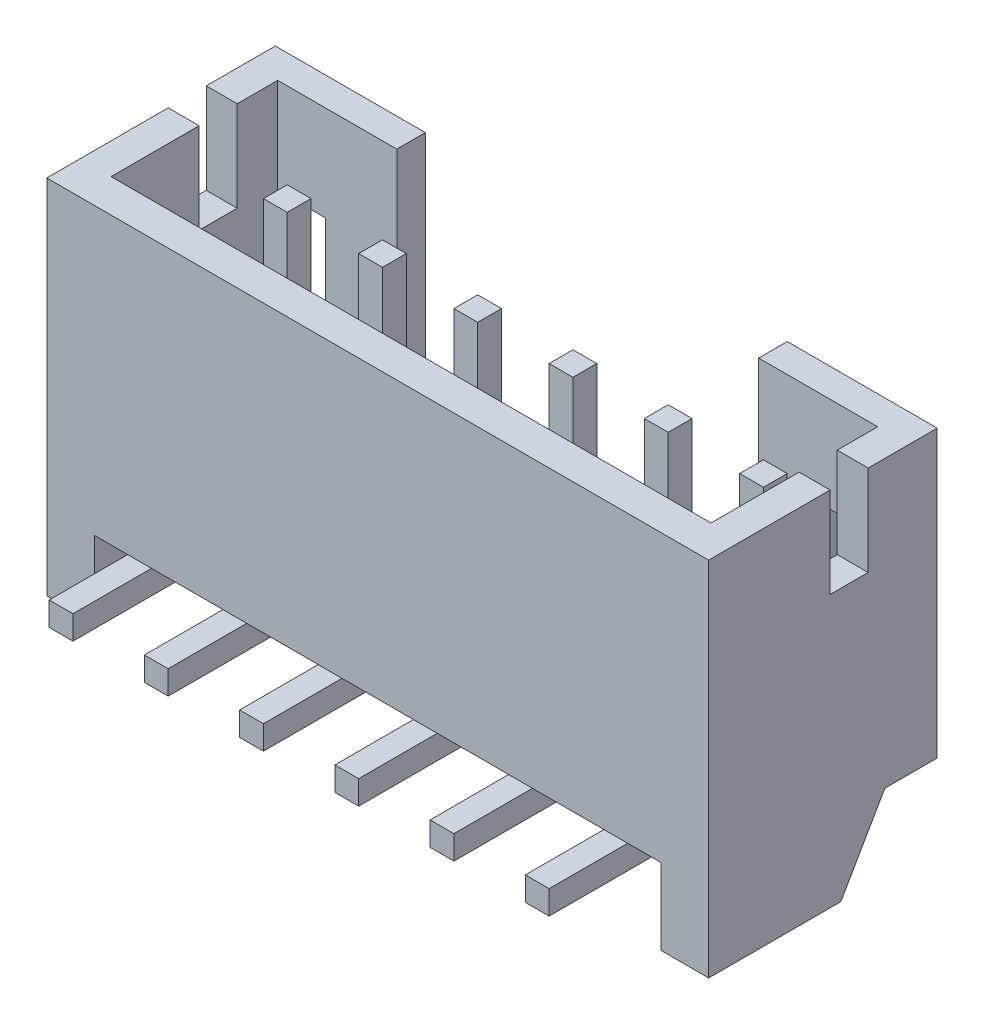
SolidWorks part; units mm, degrees
material "PE Low Density Film"
ref_plane "Front" through (0, 0, 0) normal (0, 0, 1) x (1, 0, 0)
ref_plane "Top" through (0, 0, 0) normal (0, 1, 0) x (1, 0, 0)
ref_plane "Right" through (0, 0, 0) normal (1, 0, 0) x (0, 0, -1)
sketch "Sketch1" plane through (0, 0, 0) normal (0, 1, 0) x (1, 0, 0)
  line L1 (-6.95, 2.4) -> (6.95, 2.4)
  line L2 (-6.95, 2.4) -> (-6.95, -2.4)
  line L3 (-6.95, -2.4) -> (6.95, -2.4)
  line L4 (6.95, 2.4) -> (6.95, -2.4)
  point P4 (6.95, 0)
  point P5 (0, 2.4)
  dimension "D1" = 13.9
  dimension "D2" = 4.8
extrude "Boss-Extrude1" add sketch "Sketch1" along normal blind 6 separate body
sketch "Sketch2" plane through (0, 6, 0) normal (0, 1, 0) x (1, 0, 0)
  line L1 (-6.3, 1.8) -> (6.3, 1.8)
  line L2 (-6.3, 1.8) -> (-6.3, -1.7)
  line L3 (-6.3, -1.7) -> (6.3, -1.7)
  line L4 (6.3, 1.8) -> (6.3, -1.7)
  line L5 (6.95, 2.4) -> (-6.95, 2.4) construction
  line L6 (-6.95, -2.4) -> (6.95, -2.4) construction
  line L7 (6.95, -2.4) -> (6.95, 2.4) construction
  line L8 (0, 0) -> (0, 4.3297) construction
  dimension "D1" = 0.6
  dimension "D2" = 0.7
  dimension "D3" = 0.65
extrude "Cut-Extrude1" cut sketch "Sketch2" against normal blind 4.25
sketch "Sketch4" plane through (0, 0, 0) normal (0, -1, 0) x (1, 0, 0)
  line L0 (0, 5.2091) -> (0, 0) construction
  line L1 (-6.95, 2.4) -> (6.95, 2.4) construction
  line L2 (-6.95, 2.4) -> (-5.95, 2.4)
  line L3 (-6.95, 2.4) -> (-6.95, -2.4)
  line L4 (-6.95, -2.4) -> (-5.95, -2.4)
  line L5 (-5.95, 2.4) -> (-5.95, -2.4)
  line L6 (-6.95, -2.4) -> (-6.95, 2.4) construction
  line L9 (6.95, -2.4) -> (-6.95, -2.4) construction
  line L10 (6.95, 2.4) -> (5.95, 2.4)
  line L11 (5.95, 2.4) -> (5.95, -2.4)
  line L12 (6.95, -2.4) -> (5.95, -2.4)
  line L13 (6.95, 2.4) -> (6.95, -2.4)
  dimension "D1" = 1
extrude "Boss-Extrude2" add sketch "Sketch4" along normal blind 1.6
sketch "Sketch5" plane through (-6.95, 0, 0) normal (-1, 0, 0) x (0, 0, 1)
  line L0 (-2.4, 0) -> (-1.3, 0)
  line L1 (-1.3, 0) -> (-0.3762, -1.6)
  line L2 (-0.3762, -1.6) -> (-2.4, -1.6)
  line L3 (-2.4, -1.6) -> (-2.4, 0)
  line L4 (-2.4, 6) -> (2.4, 6) construction
  line L5 (-0.95, 6) -> (-0.15, 6)
  line L6 (-0.95, 6) -> (-0.95, 4.1)
  line L7 (-0.95, 4.1) -> (-0.15, 4.1)
  line L8 (-0.15, 6) -> (-0.15, 4.1)
  line L9 (-2.4, 6) -> (-2.4, -1.6) construction
  line L11 (2.4, -1.6) -> (-2.4, -1.6) construction
  dimension "D1" = 1.45
  dimension "D2" = 1.9
  dimension "D3" = 0.8
  dimension "D4" = 1.1
  dimension "D6" = 60
extrude "Cut-Extrude3" cut sketch "Sketch5" against normal through all
sketch "Sketch3" plane through (0, 0, -2.4) normal (0, 0, -1) x (-1, 0, 0)
  line L0 (-6.95, 6) -> (6.95, 6) construction
  line L1 (-6.3, 4) -> (-5.3, 4)
  line L2 (-6.3, 4) -> (-6.3, 0)
  line L3 (-6.3, 0) -> (-5.3, 0)
  line L4 (-5.3, 4) -> (-5.3, 0)
  line L5 (-3.8, 6) -> (3.8, 6)
  line L6 (-3.8, 6) -> (-3.8, 1.75)
  line L7 (-3.8, 1.75) -> (3.8, 1.75)
  line L8 (3.8, 6) -> (3.8, 1.75)
  line L9 (-6.95, 0) -> (6.95, 0) construction
  line L10 (0, 6) -> (0, 0) construction
  line L11 (0, 0) -> (10.285, 0) construction
  line L12 (6.3, 1.75) -> (-6.3, 1.75) construction
  line L13 (6.3, 4) -> (5.3, 4)
  line L14 (6.3, 4) -> (6.3, 0)
  line L15 (6.3, 0) -> (5.3, 0)
  line L16 (5.3, 4) -> (5.3, 0)
  dimension "D1" = 7.6
  dimension "D2" = 10.6
  dimension "D3" = 1
  dimension "D4" = 4
extrude "Cut-Extrude2" cut sketch "Sketch3" against normal up to surface (0.6 mm away) up to face at (0, 3.875, -1.8)
sketch "Sketch6" plane through (0, 0, 0) normal (1, 0, 0) x (0, 0, -1)
  line L0 (0.15, 1.75) -> (-1.7, 1.75)
  line L1 (-1.7, 1.75) -> (-1.7, 1.15)
  line L2 (-1.7, 1.15) -> (-0.45, 1.15)
  line L3 (-0.45, 1.15) -> (0.15, 1.75)
  line L5 (-1.7, 1.75) -> (-1.7, 6) construction
  line L6 (1.8, 1.75) -> (-1.7, 1.75) construction
  dimension "D1" = 45
  dimension "D2" = 1.85
  dimension "D3" = 0.6
extrude "Cut-Extrude4" cut sketch "Sketch6" against normal up to vertex (6.3 mm away) from vertex up to point (-6.3, 1.75, 1.7) starting at point (6.3, 1.75, 1.7)
sketch "Sketch7" plane through (0, 0, 0) normal (1, 0, 0) x (0, 0, -1)
  line L0 (0.45, 5.05) -> (0.95, 5.05)
  line L2 (0.95, 5.05) -> (0.95, 0)
  line L3 (0.45, -0.5) -> (-4.05, -0.5)
  line L4 (-4.05, -0.5) -> (-4.05, 0)
  line L5 (-4.05, 0) -> (0.45, 0)
  line L6 (0.45, 0) -> (0.45, 5.05)
  line L7 (0, 2.6449) -> (0, 0) construction
  arc A0 (0.95, 0) -> (0.45, -0.5) centre (0.45, 0) cw
  dimension "D4" = 0.5
  dimension "D1" = 0.45
  dimension "D2" = 0.5
  dimension "D3" = 0.5
  dimension "D5" = 4.05
  dimension "D6" = 5.05
extrude "Boss-Extrude3" add sketch "Sketch7" along normal mid plane 0.5 from offset 5 separate body
pattern_linear "LPattern1" count 6 spacing 2 along (-1, 0, 0) of bodies 110
combine bodies "Combine1" operation type add bodies to combine 114 110 112 115 109 113 111
